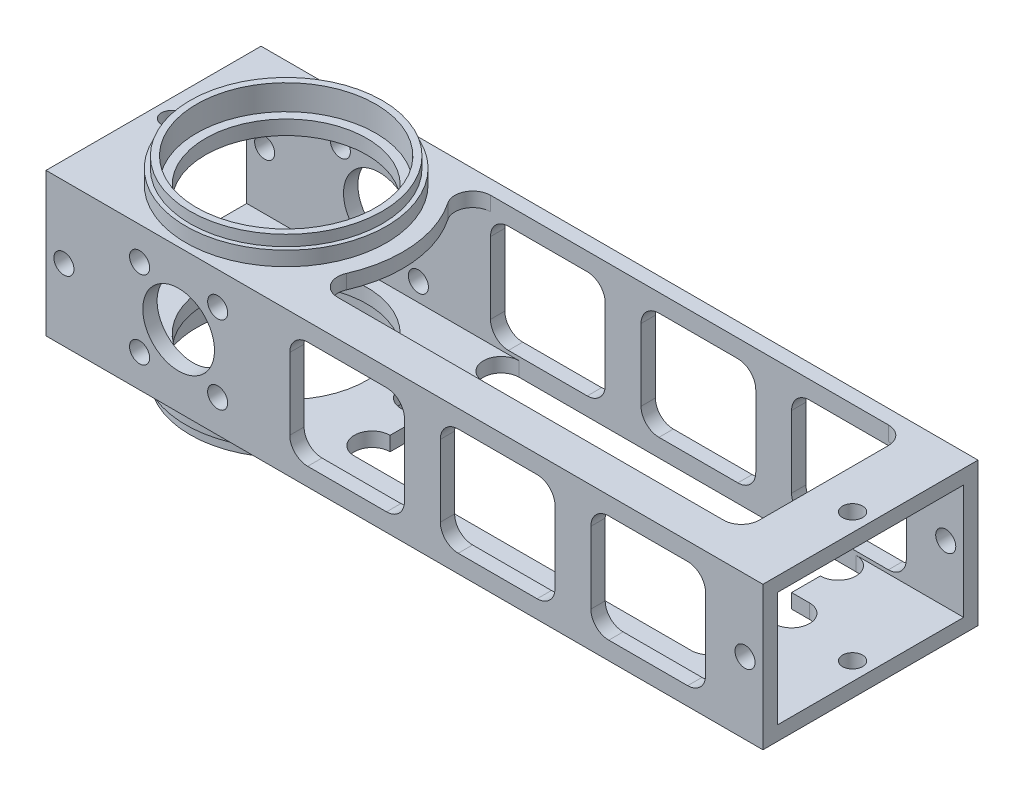
SolidWorks part; units mm, degrees
material "6061 Alloy"
ref_plane "Front Plane" through (0, 0, 0) normal (0, 0, 1) x (1, 0, 0)
ref_plane "Top Plane" through (0, 0, 0) normal (0, 1, 0) x (1, 0, 0)
ref_plane "Right Plane" through (0, 0, 0) normal (1, 0, 0) x (0, 0, -1)
sketch "Sketch1" plane through (0, 0, 0) normal (1, 0, 0) x (0, 0, -1)
  line L0 (2.54, 22.86) -> (35.56, 22.86)
  line L1 (0, 0) -> (38.1, 0)
  line L2 (0, 0) -> (0, 25.4)
  line L3 (0, 25.4) -> (38.1, 25.4)
  line L4 (38.1, 0) -> (38.1, 25.4)
  line L5 (35.56, 2.54) -> (35.56, 22.86)
  line L6 (2.54, 2.54) -> (35.56, 2.54)
  line L7 (2.54, 2.54) -> (2.54, 22.86)
  dimension "D1" = 38.1
  dimension "D2" = 25.4
  dimension "D3" = 33.02
extrude "Boss-Extrude1" add sketch "Sketch1" along normal blind 127
sketch "Sketch2" plane through (0, 25.4, 0) normal (0, 1, 0) x (1, 0, 0)
  line L0 (0, 19.05) -> (23.495, 19.05) construction
  line L1 (0, 38.1) -> (0, 0) construction
  circle A0 centre (23.495, 19.05) radius 14.2875
  dimension "D2" = 28.575
  dimension "D1" = 23.495
extrude "Cut-Extrude1" cut sketch "Sketch2" against normal through all
sketch "Sketch3" plane through (0, 0, 0) normal (0, 0, 1) x (1, 0, 0)
  line L0 (0, 12.7) -> (23.495, 12.7) construction
  line L1 (0, 25.4) -> (0, 0) construction
  line L2 (0, 25.4) -> (23.495, 25.4) construction
  line L3 (63.5, 22.225) -> (69.85, 22.225) construction
  line L4 (16.5802, 5.7852) -> (30.4098, 5.7852) construction
  line L5 (16.5802, 5.7852) -> (16.5802, 19.6148) construction
  line L6 (16.5802, 19.6148) -> (30.4098, 19.6148) construction
  line L7 (30.4098, 5.7852) -> (30.4098, 19.6148) construction
  line L8 (16.5802, 5.7852) -> (30.4098, 19.6148) construction
  line L9 (16.5802, 19.6148) -> (30.4098, 5.7852) construction
  line L10 (46.355, 22.225) -> (60.325, 22.225)
  line L11 (43.18, 19.05) -> (43.18, 6.35)
  line L12 (46.355, 3.175) -> (60.325, 3.175)
  line L13 (63.5, 19.05) -> (63.5, 6.35)
  line L14 (73.025, 22.225) -> (86.995, 22.225)
  line L15 (69.85, 19.05) -> (69.85, 6.35)
  line L16 (73.025, 3.175) -> (86.995, 3.175)
  line L17 (90.17, 19.05) -> (90.17, 6.35)
  line L18 (99.695, 22.225) -> (113.665, 22.225)
  line L19 (96.52, 19.05) -> (96.52, 6.35)
  line L20 (99.695, 3.175) -> (113.665, 3.175)
  line L21 (116.84, 19.05) -> (116.84, 6.35)
  line L22 (90.17, 22.225) -> (96.52, 22.225) construction
  line L23 (127, 12.7) -> (116.84, 12.7) construction
  line L24 (127, 25.4) -> (127, 0) construction
  circle A0 centre (23.495, 12.7) radius 6.35
  circle A1 centre (16.5802, 19.6148) radius 1.778
  circle A2 centre (16.5802, 5.7852) radius 1.778
  circle A3 centre (30.4098, 5.7852) radius 1.778
  circle A4 centre (30.4098, 19.6148) radius 1.778
  arc A5 (113.665, 22.225) -> (116.84, 19.05) centre (113.665, 19.05) cw
  arc A6 (113.665, 3.175) -> (116.84, 6.35) centre (113.665, 6.35) ccw
  arc A7 (96.52, 6.35) -> (99.695, 3.175) centre (99.695, 6.35) ccw
  arc A8 (99.695, 22.225) -> (96.52, 19.05) centre (99.695, 19.05) ccw
  arc A9 (86.995, 22.225) -> (90.17, 19.05) centre (86.995, 19.05) cw
  arc A10 (86.995, 3.175) -> (90.17, 6.35) centre (86.995, 6.35) ccw
  arc A11 (69.85, 6.35) -> (73.025, 3.175) centre (73.025, 6.35) ccw
  arc A12 (73.025, 22.225) -> (69.85, 19.05) centre (73.025, 19.05) ccw
  arc A13 (60.325, 22.225) -> (63.5, 19.05) centre (60.325, 19.05) cw
  arc A14 (60.325, 3.175) -> (63.5, 6.35) centre (60.325, 6.35) ccw
  arc A15 (43.18, 6.35) -> (46.355, 3.175) centre (46.355, 6.35) ccw
  arc A16 (46.355, 22.225) -> (43.18, 19.05) centre (46.355, 19.05) ccw
  point P33 (116.84, 22.225)
  point P36 (116.84, 3.175)
  dimension "D1" = 12.7
  dimension "D3" = 3.556
  dimension "D8" = 3.175
  dimension "D2" = 19.558
  dimension "D4" = 20.32
  dimension "D5" = 19.05
  dimension "D6" = 6.35
  dimension "D7" = 10.16
extrude "Cut-Extrude2" cut sketch "Sketch3" against normal through all
sketch "Sketch4" plane through (0, 25.4, 0) normal (0, 1, 0) x (1, 0, 0)
  line L0 (45.3195, 6.35) -> (113.665, 6.35)
  line L1 (116.84, 9.525) -> (116.84, 32.385)
  line L2 (113.665, 35.56) -> (43.2235, 35.56)
  line L3 (116.84, 19.05) -> (127, 19.05) construction
  line L4 (127, 38.1) -> (127, 0) construction
  line L5 (127, 0) -> (116.84, 0) construction
  line L6 (127, 38.1) -> (0, 38.1) construction
  line L7 (127, 0) -> (0, 0) construction
  line L8 (79.4923, 6.35) -> (79.4923, 35.56) construction
  arc A0 (42.4096, 10.795) -> (40.593, 30.607) centre (23.495, 19.05) ccw
  circle A1 centre (23.495, 19.05) radius 14.2875 construction
  arc A2 (113.665, 6.35) -> (116.84, 9.525) centre (113.665, 9.525) ccw
  arc A3 (116.84, 32.385) -> (113.665, 35.56) centre (113.665, 32.385) ccw
  arc A4 (40.593, 30.607) -> (43.2235, 35.56) centre (43.2235, 32.385) cw
  arc A5 (42.4096, 10.795) -> (45.3195, 6.35) centre (45.3195, 9.525) ccw
  dimension "D3" = 6.35
  dimension "D4" = 3.175
  dimension "D1" = 2.54
  dimension "D2" = 6.35
extrude "Cut-Extrude3" cut sketch "Sketch4" against normal up to next
hole_wizard "#4 (0.209) Diameter Hole1" positions "3DSketch1" profile "Sketch5" hole size "#4" standard "ANSI Inch" end condition up to next
sketch3d "3DSketch1"
  line L0 (127, 25.4, -19.05) -> (123.825, 25.4, -19.05) construction
  line L1 (127, 25.4, -38.1) -> (127, 25.4, 0) construction
  line L6 (127, 12.7, 0) -> (123.825, 12.7, 0) construction
  line L7 (127, 25.4, 0) -> (127, 0, 0) construction
  line L13 (0, 25.4, -19.05) -> (3.175, 25.4, -19.05) construction
  line L14 (0, 25.4, -38.1) -> (0, 25.4, 0) construction
  line L17 (0, 12.7, 0) -> (3.175, 12.7, 0) construction
  line L18 (0, 25.4, 0) -> (0, 0, 0) construction
  point P13 (123.825, 12.7, 0)
  point P24 (3.175, 25.4, -19.05)
  point P30 (3.175, 12.7, 0)
  point P48 (3.175, 25.4, -19.05)
  point P67 (3.175, 25.4, -19.05)
  point P69 (3.175, 12.7, 0)
  point P77 (123.825, 25.4, -19.05)
  point P79 (123.825, 12.7, 0)
  point P81 (123.825, 0, -19.05)
  point P83 (123.825, 12.7, -38.1)
  point P90 (3.175, 12.7, -38.1)
  point P92 (3.175, 0, -19.05)
  dimension "D1" = 3.175
sketch "Sketch5" plane through (3.175, 25.4, -19.05) normal (1, 0, 0) x (0, 0, 1)
  line L0 (0, 0) -> (0, 2.541)
  line L1 (0, 2.541) -> (1.778, 2.541)
  line L2 (1.778, 2.541) -> (1.778, 0)
  line L5 (1.778, 0) -> (0, 0)
  line L11 (0, -6.35) -> (0, 107.95) construction
  dimension "Thru Hole Dia." = 3.556
  dimension "Thru Hole Depth" = 2.541
sketch "Sketch6" plane through (0, 0, 0) normal (0, -1, 0) x (1, 0, 0)
  line L0 (48.26, -35.56) -> (107.95, -35.56)
  line L1 (48.26, -6.35) -> (107.95, -6.35)
  line L2 (79.4923, -6.35) -> (79.4923, -35.56) construction
  line L3 (113.665, -35.56) -> (43.2235, -35.56) construction
  line L4 (127, 0) -> (127, -38.1) construction
  line L5 (48.26, -6.35) -> (48.26, -35.56) construction
  line L6 (107.95, -6.35) -> (107.95, -35.56) construction
  line L8 (107.95, -12.7) -> (107.95, -17.78)
  line L9 (107.95, -17.78) -> (111.125, -17.78)
  line L10 (107.95, -29.21) -> (107.95, -24.13)
  line L11 (107.95, -24.13) -> (111.125, -24.13)
  line L12 (48.26, -29.21) -> (48.26, -24.13)
  line L13 (48.26, -12.7) -> (48.26, -17.78)
  line L14 (48.26, -17.78) -> (45.085, -17.78)
  line L15 (48.26, -24.13) -> (45.085, -24.13)
  arc A0 (107.95, -6.35) -> (107.95, -12.7) centre (107.95, -9.525) cw
  arc A1 (107.95, -35.56) -> (107.95, -29.21) centre (107.95, -32.385) ccw
  arc A2 (48.26, -35.56) -> (48.26, -29.21) centre (48.26, -32.385) cw
  arc A3 (48.26, -6.35) -> (48.26, -12.7) centre (48.26, -9.525) ccw
  arc A5 (111.125, -17.78) -> (111.125, -24.13) centre (111.125, -20.955) cw
  arc A6 (45.085, -17.78) -> (45.085, -24.13) centre (45.085, -20.955) ccw
  dimension "D1" = 59.69
  dimension "D2" = 3.175
  dimension "D3" = 3.175
  dimension "D4" = 19.05
extrude "Cut-Extrude4" cut sketch "Sketch6" against normal up to next
ref_plane "Plane1" through (0, 0, -19.05) normal (0, 0, 1) x (1, 0, 0)
sketch "Sketch7" plane through (0, 0, -19.05) normal (0, 0, 1) x (1, 0, 0)
  line L0 (23.495, -4.445) -> (23.495, 29.845) construction
  line L1 (39.37, 29.845) -> (39.37, 25.4)
  line L2 (39.37, 25.4) -> (41.275, 25.4)
  line L3 (41.275, 25.4) -> (41.275, 27.94)
  line L4 (41.275, 27.94) -> (40.513, 27.94)
  line L5 (40.513, 27.94) -> (40.513, 29.845)
  line L6 (40.513, 29.845) -> (39.37, 29.845)
  line L7 (39.37, -4.445) -> (39.37, 0)
  line L12 (39.37, 0) -> (41.275, 0)
  line L13 (41.275, 0) -> (41.275, -2.54)
  line L14 (41.275, -2.54) -> (40.513, -2.54)
  line L15 (40.513, -2.54) -> (40.513, -4.445)
  line L16 (40.513, -4.445) -> (39.37, -4.445)
  line L17 (127, 25.4) -> (0, 25.4) construction
  dimension "D1" = 35.56
  dimension "D2" = 31.75
  dimension "D3" = 34.036
  dimension "D4" = 4.445
  dimension "D5" = 2.54
revolve "Revolve1" add sketch "Sketch7" angle 360 about L0
